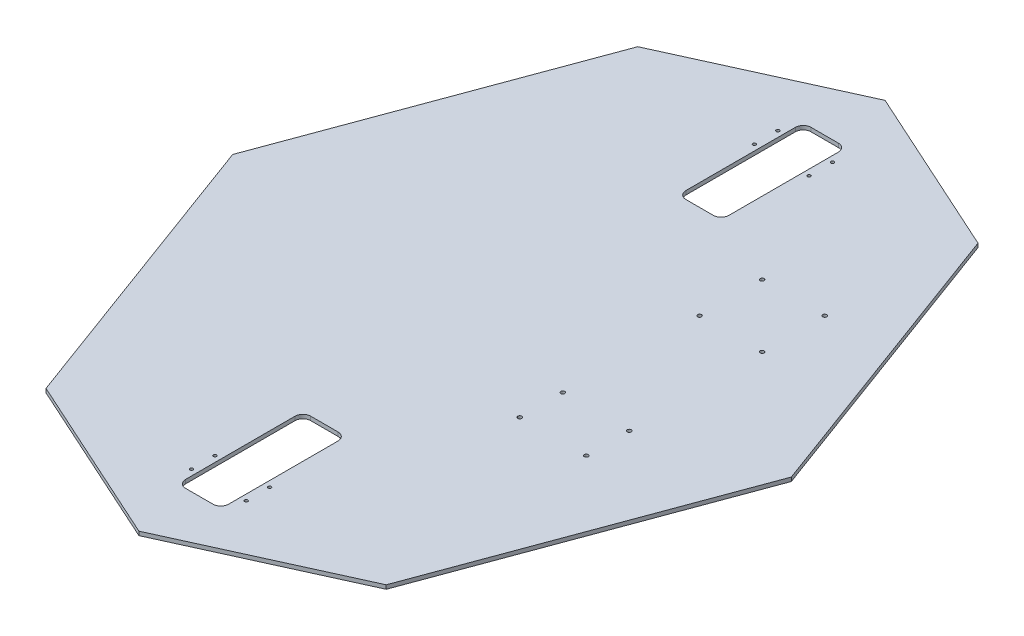
SolidWorks part; units mm, degrees
material "AISI 1020"
ref_plane "Front Plane" through (0, 0, 0) normal (0, 0, 1) x (1, 0, 0)
ref_plane "Top Plane" through (0, 0, 0) normal (0, 1, 0) x (1, 0, 0)
ref_plane "Right Plane" through (0, 0, 0) normal (1, 0, 0) x (0, 0, -1)
sketch "Sketch1" plane through (0, 0, 0) normal (0, 1, 0) x (1, 0, 0)
  line L0 (0, -483.0506) -> (0, 483.0506) construction
  line L1 (-276.37, 480.7072) -> (-453.8156, 0)
  line L2 (-276.37, -480.7072) -> (-453.8156, 0)
  line L3 (0, -606.1134) -> (-276.37, -480.7072)
  line L4 (276.37, -480.7072) -> (0, -606.1134)
  line L5 (278.8894, 0) -> (-278.8894, 0) construction
  line L6 (276.37, -480.7072) -> (453.8156, 0)
  line L7 (453.8156, 0) -> (276.37, 480.7072)
  line L8 (276.37, 480.7072) -> (0, 606.1134)
  line L9 (-276.37, 480.7072) -> (0, 606.1134)
  line L23 (-278.8894, -483.0506) -> (-457.2, 0) construction
  line L24 (0, -609.6) -> (-278.8894, -483.0506) construction
  line L25 (278.8894, -483.0506) -> (0, -609.6) construction
  line L26 (278.8894, -483.0506) -> (457.2, 0) construction
  line L27 (457.2, 0) -> (278.8894, 483.0506) construction
  line L28 (278.8894, 483.0506) -> (0, 609.6) construction
  line L29 (-278.8894, 483.0506) -> (0, 609.6) construction
  line L30 (-278.8894, 483.0506) -> (-457.2, 0) construction
  line L39 (-278.8894, -483.0506) -> (278.8894, -483.0506) construction
  line L40 (-278.8894, -483.0506) -> (-278.8894, 483.0506) construction
  line L41 (-278.8894, 483.0506) -> (278.8894, 483.0506) construction
  line L42 (278.8894, -483.0506) -> (278.8894, 483.0506) construction
  line L43 (-278.8894, -483.0506) -> (278.8894, 483.0506) construction
  line L44 (-278.8894, 483.0506) -> (278.8894, -483.0506) construction
  ellipse E0 centre (0, 0) end of major axis (0, 609.6) minor radius 457.2 construction
  point P50 (0, 0)
  dimension "D1" = 3.175
  dimension "D3" = 30
  dimension "D8" = 609.6
  dimension "D9" = 457.2
extrude "Boss-Extrude1" add sketch "Sketch1" along normal mid plane 6.35
sketch "Sketch2" plane through (0, 0, 0) normal (0, 1, 0) x (1, 0, 0)
  line L1 (82.55, -457.2) -> (-82.55, -457.2) construction
  line L2 (82.55, -457.2) -> (82.55, 457.2) construction
  line L3 (82.55, 457.2) -> (-82.55, 457.2) construction
  line L4 (-82.55, -457.2) -> (-82.55, 457.2) construction
  line L5 (0, 457.2) -> (0, -457.2) construction
  line L6 (44.45, 438.15) -> (-44.45, 438.15) construction
  line L7 (-34.925, 304.8) -> (34.925, 304.8)
  line L8 (-34.925, 304.8) -> (-34.925, 508)
  line L9 (-34.925, 508) -> (34.925, 508)
  line L10 (34.925, 304.8) -> (34.925, 508)
  line L11 (44.45, 438.15) -> (44.45, 476.25) construction
  line L17 (-82.55, 0) -> (82.55, 0) construction
  line L18 (44.45, 476.25) -> (-44.45, 476.25) construction
  line L19 (-44.45, 438.15) -> (-44.45, 476.25) construction
  line L22 (44.45, 438.15) -> (-44.45, 476.25) construction
  line L23 (44.45, 476.25) -> (-44.45, 438.15) construction
  circle A0 centre (-44.45, 476.25) radius 2.54
  circle A1 centre (-44.45, 438.15) radius 2.54
  circle A2 centre (44.45, 438.15) radius 2.54
  circle A3 centre (44.45, 476.25) radius 2.54
  point P0 (0, 0)
  point P36 (0, 0)
  dimension "D7" = 5.08
  dimension "D1" = 165.1
  dimension "D2" = 914.4
  dimension "D3" = 69.85
  dimension "D4" = 203.2
  dimension "D5" = 34.925
  dimension "D6" = 38.1
  dimension "D8" = 50.8
  dimension "D10" = 88.9
extrude "Cut-Extrude1" cut sketch "Sketch2" against normal through all both and the other way through all contours L10 L9 L8 L7 | A3 | A2 | A1 | A0
fillet "Fillet1" radius 12.7 4 edges at (-34.925, 0, -508) (34.925, 0, -508) (34.925, 0, -304.8) (-34.925, 0, -304.8)
sketch "Sketch4" plane through (0, 3.175, 0) normal (0, 1, 0) x (1, 0, 0)
  line L1 (149.225, -66.675) -> (257.175, -66.675) construction
  line L2 (149.225, -66.675) -> (149.225, -136.525) construction
  line L3 (149.225, -136.525) -> (257.175, -136.525) construction
  line L4 (257.175, -66.675) -> (257.175, -136.525) construction
  line L5 (149.225, -66.675) -> (257.175, -136.525) construction
  line L6 (149.225, -136.525) -> (257.175, -66.675) construction
  line L7 (152.4, 254) -> (254, 254) construction
  line L8 (152.4, 254) -> (152.4, 152.4) construction
  line L9 (152.4, 152.4) -> (254, 152.4) construction
  line L10 (254, 254) -> (254, 152.4) construction
  line L11 (152.4, 254) -> (254, 152.4) construction
  line L12 (152.4, 152.4) -> (254, 254) construction
  circle A0 centre (257.175, -66.675) radius 3.175
  circle A1 centre (149.225, -66.675) radius 3.175
  circle A2 centre (149.225, -136.525) radius 3.175
  circle A3 centre (257.175, -136.525) radius 3.175
  circle A4 centre (152.4, 254) radius 3.175
  circle A5 centre (254, 254) radius 3.175
  circle A6 centre (254, 152.4) radius 3.175
  circle A7 centre (152.4, 152.4) radius 3.175
  point P0 (203.2, -101.6)
  point P9 (203.2, 203.2)
  dimension "D1" = 6.35
  dimension "D8" = 6.35
  dimension "D2" = 107.95
  dimension "D3" = 69.85
  dimension "D4" = 101.6
  dimension "D5" = 203.2
  dimension "D6" = 101.6
  dimension "D7" = 304.8
extrude "Cut-Extrude3" cut sketch "Sketch4" against normal up to next
mirror "Mirror1" about plane through (0, 0, 0) normal (0, 0, 1) of "Fillet1", "Cut-Extrude1"
